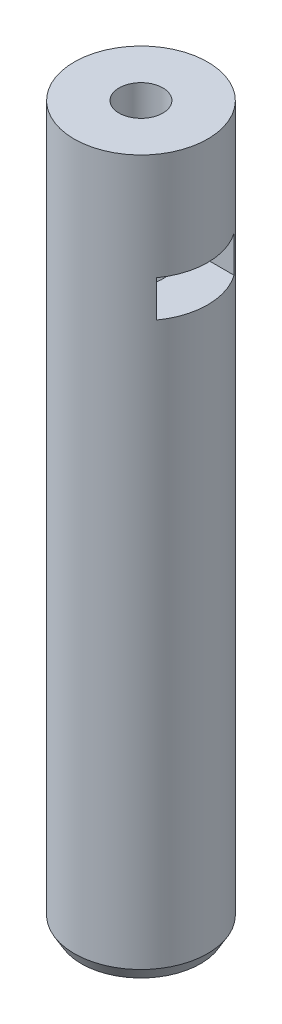
SolidWorks part; units mm, degrees
ref_plane "Front Plane" through (0, 0, 0) normal (0, 0, 1) x (1, 0, 0)
ref_plane "Top Plane" through (0, 0, 0) normal (0, 1, 0) x (1, 0, 0)
ref_plane "Right Plane" through (0, 0, 0) normal (1, 0, 0) x (0, 0, -1)
sketch "Sketch2" plane through (0, 0, 0) normal (0, 1, 0) x (1, 0, 0)
  circle A0 centre (0, 0) radius 9.3
  dimension "D1" = 18.6
extrude "Boss-Extrude1" add sketch "Sketch2" along normal blind 100
sketch "Sketch3" plane through (0, 100, 0) normal (0, 1, 0) x (1, 0, 0)
  circle A0 centre (0, 0) radius 3.05
  dimension "D1" = 6.1
chamfer "Chamfer1" distance 1 angle 60 1 edges at (0, 0, 9.3) first distance on face at (0, 0, 9.3)
extrude "Cut-Extrude1" cut sketch "Sketch3" against normal blind 25
ref_plane "Plane1" through (0, 80, 0) normal (0, 1, 0) x (1, 0, 0)
sketch "Sketch4" plane through (0, 80, 0) normal (0, 1, 0) x (1, 0, 0)
  line L0 (9.3, 0) -> (-9.3, 0) construction
  line L14 (3.12, 5.404) -> (7.5688, 5.404)
  line L16 (3.12, 5.404) -> (-3.12, 5.404)
  line L17 (-3.12, 5.404) -> (-6.24, 0)
  line L18 (-6.24, 0) -> (-3.12, -5.404)
  line L19 (-3.12, -5.404) -> (3.12, -5.404)
  line L21 (3.12, -5.404) -> (7.5688, -5.404)
  line L23 (6.24, 0) -> (4.68, 2.702) [skipped]
  line L24 (3.12, -5.404) -> (4.68, -2.702) [skipped]
  circle A0 centre (0, 0) radius 9.3 construction
  arc A2 (0, 5.404) -> (0, -5.404) centre (0, 0) ccw construction
  arc A3 (7.5688, -5.404) -> (7.5688, 5.404) centre (0, 0) ccw
  dimension "D1" = 6.24
extrude "Cut-Extrude2" cut sketch "Sketch4" along normal blind 5.1
